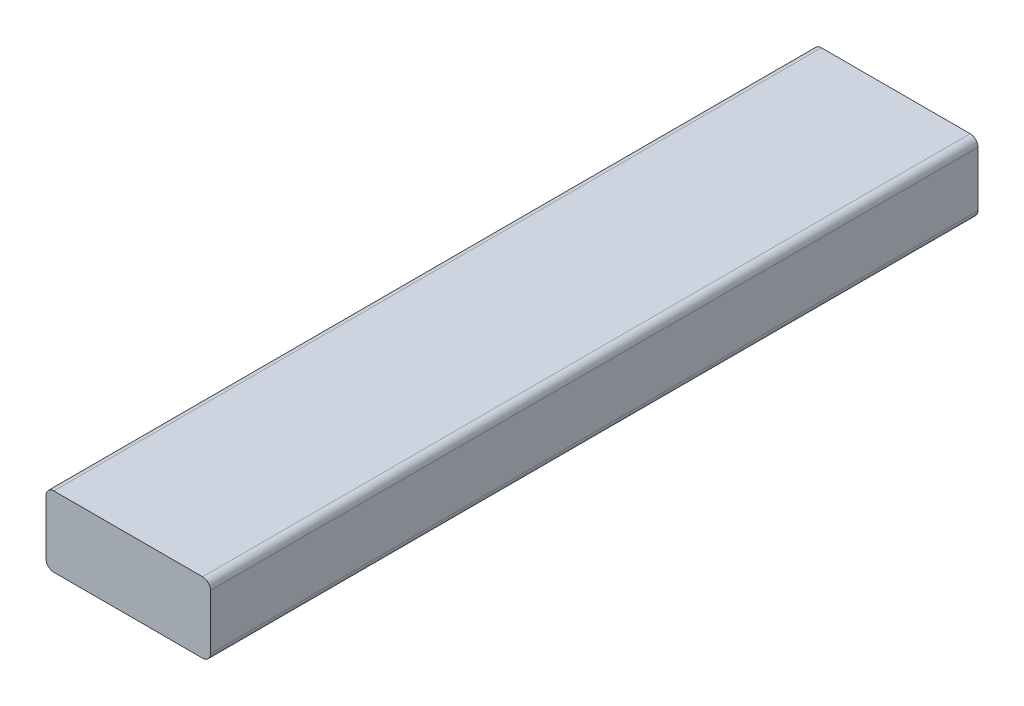
SolidWorks part; units mm, degrees
ref_plane "Front Plane" through (0, 0, 0) normal (0, 0, 1) x (1, 0, 0)
ref_plane "Top Plane" through (0, 0, 0) normal (0, 1, 0) x (1, 0, 0)
ref_plane "Right Plane" through (0, 0, 0) normal (1, 0, 0) x (0, 0, -1)
sketch "Sketch1" plane through (0, 0, 0) normal (0, 0, 1) x (1, 0, 0)
  line L1 (0, 0) -> (42, 0)
  line L2 (0, 0) -> (0, 18)
  line L3 (0, 18) -> (42, 18)
  line L4 (42, 0) -> (42, 18)
  dimension "D1" = 42
  dimension "D2" = 18
extrude "Boss-Extrude1" add sketch "Sketch1" along normal blind 196
fillet "Fillet1" radius 2 4 edges at (0, 0, 98) (42, 0, 98) (42, 18, 98) (0, 18, 98)
